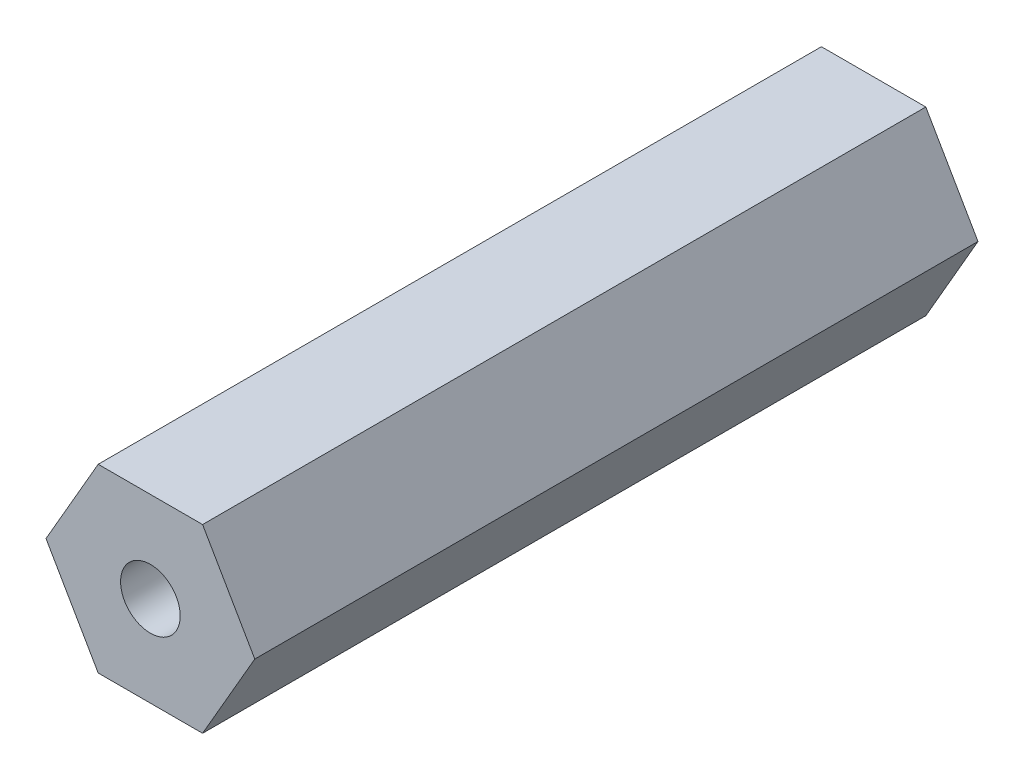
SolidWorks part; units mm, degrees
ref_plane "Front" through (0, 0, 0) normal (0, 0, 1) x (1, 0, 0)
ref_plane "Top" through (0, 0, 0) normal (0, 1, 0) x (1, 0, 0)
ref_plane "Right" through (0, 0, 0) normal (1, 0, 0) x (0, 0, -1)
sketch "Esquisse1" plane through (0, 0, 0) normal (0, 0, 1) x (1, 0, 0)
  line L1 (5.7735, 0) -> (2.8868, 5)
  line L2 (2.8868, 5) -> (-2.8868, 5)
  line L3 (-2.8868, 5) -> (-5.7735, 0)
  line L4 (-5.7735, 0) -> (-2.8868, -5)
  line L5 (-2.8868, -5) -> (2.8868, -5)
  line L6 (2.8868, -5) -> (5.7735, 0)
  circle A0 centre (0, 0) radius 5 construction
  dimension "D1" = 10
extrude "Boss.-Extru.1" add sketch "Esquisse1" along normal blind 40
sketch "Esquisse2" plane through (0, 0, 40) normal (0, 0, 1) x (1, 0, 0)
  circle A0 centre (0, 0) radius 1.65
  dimension "D1" = 3.3
extrude "Enlèv. mat.-Extru.1" cut sketch "Esquisse2" against normal blind 9
extrude "Enlèv. mat.-Extru.2" cut sketch "Esquisse2<2>" along normal blind 9 from vertex starting at point (2.8868, 5, 0)
sketch "Esquisse2<2>" plane through (0, 0, 40) normal (0, 0, 1) x (1, 0, 0) same geometry as "Esquisse2"
